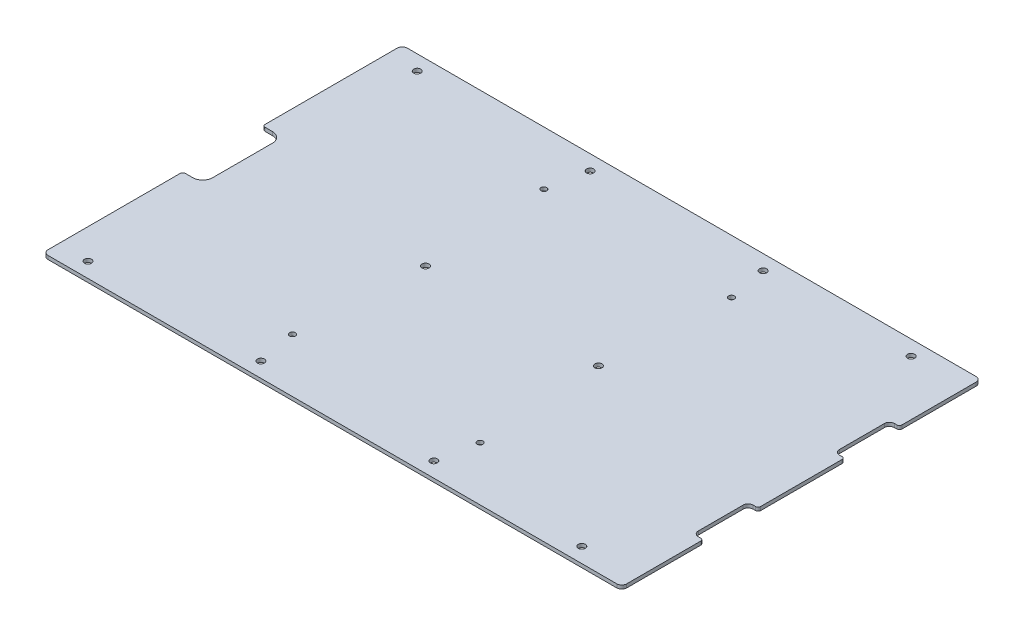
SolidWorks part; units mm, degrees
material "1060 Alloy"
ref_plane "Front" through (0, 0, 0) normal (0, 0, 1) x (1, 0, 0)
ref_plane "Top" through (0, 0, 0) normal (0, 1, 0) x (1, 0, 0)
ref_plane "Right" through (0, 0, 0) normal (1, 0, 0) x (0, 0, -1)
sketch "Sketch1" plane through (0, 0, 0) normal (0, 1, 0) x (1, 0, 0)
  line L0 (-55.0333, 0) -> (-165.1, 0) construction
  line L1 (-180.975, 114.3) -> (180.975, 114.3)
  line L2 (-184.15, 111.125) -> (-184.15, -111.125)
  line L3 (-180.975, -114.3) -> (180.975, -114.3)
  line L4 (184.15, 111.125) -> (184.15, -111.125)
  line L5 (-184.15, 114.3) -> (184.15, -114.3) construction
  line L6 (-184.15, -114.3) -> (184.15, 114.3) construction
  line L7 (-165.1, -104.775) -> (165.1, -104.775) construction
  line L8 (-165.1, -104.775) -> (-165.1, 104.775) construction
  line L9 (-165.1, 104.775) -> (165.1, 104.775) construction
  line L10 (165.1, -104.775) -> (165.1, 104.775) construction
  line L11 (-165.1, -104.775) -> (165.1, 104.775) construction
  line L12 (-165.1, 104.775) -> (165.1, -104.775) construction
  line L13 (-55.0333, -104.775) -> (55.0333, -104.775) construction
  line L14 (-55.0333, -104.775) -> (-55.0333, 104.775) construction
  line L15 (-55.0333, 104.775) -> (55.0333, 104.775) construction
  line L16 (55.0333, -104.775) -> (55.0333, 104.775) construction
  line L17 (-55.0333, -104.775) -> (55.0333, 104.775) construction
  line L18 (-55.0333, 104.775) -> (55.0333, -104.775) construction
  line L19 (55.0333, 0) -> (165.1, 0) construction
  line L20 (-55.0333, 0) -> (55.0333, 0) construction
  line L31 (-59.69, 80.01) -> (59.69, 80.01) construction
  line L32 (149.225, -104.775) -> (149.225, 104.775) construction
  line L33 (-59.69, 80.01) -> (-59.69, -80.01) construction
  line L34 (-59.69, -80.01) -> (59.69, -80.01) construction
  line L35 (59.69, 80.01) -> (59.69, -80.01) construction
  line L36 (-59.69, 80.01) -> (59.69, -80.01) construction
  line L37 (-59.69, -80.01) -> (59.69, 80.01) construction
  circle A0 centre (-165.1, 104.775) radius 2.2479
  circle A1 centre (-55.0333, 104.775) radius 2.2479
  circle A2 centre (55.0333, 104.775) radius 2.2479
  circle A3 centre (165.1, 104.775) radius 2.2479 construction
  circle A4 centre (165.1, -104.775) radius 2.2479 construction
  circle A5 centre (55.0333, -104.775) radius 2.2479
  circle A6 centre (-55.0333, -104.775) radius 2.2479
  circle A7 centre (-165.1, -104.775) radius 2.2479
  circle A12 centre (-55.0333, 0) radius 2.2479
  circle A13 centre (55.0333, 0) radius 2.2479
  arc A14 (184.15, 111.125) -> (180.975, 114.3) centre (180.975, 111.125) ccw
  arc A15 (184.15, -111.125) -> (180.975, -114.3) centre (180.975, -111.125) cw
  arc A16 (-180.975, -114.3) -> (-184.15, -111.125) centre (-180.975, -111.125) cw
  arc A17 (-180.975, 114.3) -> (-184.15, 111.125) centre (-180.975, 111.125) ccw
  circle A24 centre (149.225, -104.775) radius 2.2479
  circle A25 centre (149.225, 104.775) radius 2.2479
  circle A26 centre (59.69, -80.01) radius 1.8288
  circle A27 centre (-59.69, -80.01) radius 1.8288
  circle A28 centre (-59.69, 80.01) radius 1.8288
  circle A29 centre (59.69, 80.01) radius 1.8288
  point P0 (0, 0)
  point P6 (0, 0)
  point P11 (0, 0)
  point P28 (0, 0)
  point P29 (0, 0)
  point P32 (0, 0)
  dimension "D5" = 4.4958
  dimension "D8" = 3.6576
  dimension "D11" = 3.175
  dimension "D1" = 368.3
  dimension "D2" = 228.6
  dimension "D3" = 9.525
  dimension "D4" = 19.05
  dimension "D6" = 160.02
  dimension "D7" = 34.925
  dimension "D9" = 119.38
extrude "Boss-Extrude1" add sketch "Sketch1" along normal blind 2.286
sketch "Sketch2" plane through (0, 0, 0) normal (0, -1, 0) x (1, 0, 0)
  line L5 (184.15, 111.125) -> (184.15, -111.125) construction
  line L6 (184.15, 62.4205) -> (180.975, 62.4205)
  line L7 (184.15, 62.4205) -> (184.15, 27.4955)
  line L8 (184.15, 27.4955) -> (180.975, 27.4955)
  line L9 (177.8, 59.2455) -> (177.8, 30.6705)
  line L10 (-184.15, 0) -> (183.134, 0) construction
  line L11 (-184.15, -111.125) -> (-184.15, 111.125) construction
  line L12 (183.134, -115.824) -> (183.134, 115.824) construction
  line L13 (177.8, 44.958) -> (184.15, 44.958) construction
  line L14 (184.15, -27.4955) -> (180.975, -27.4955)
  line L15 (184.15, -62.4205) -> (184.15, -27.4955)
  line L16 (177.8, -59.2455) -> (177.8, -30.6705)
  line L17 (184.15, -62.4205) -> (180.975, -62.4205)
  line L19 (-184.15, 25.4) -> (-177.8, 25.4)
  line L20 (-184.15, 25.4) -> (-184.15, -25.4)
  line L21 (-184.15, -25.4) -> (-177.8, -25.4)
  line L22 (-171.45, 19.05) -> (-171.45, -19.05)
  arc A0 (180.975, -62.4205) -> (177.8, -59.2455) centre (180.975, -59.2455) cw
  arc A1 (177.8, -30.6705) -> (180.975, -27.4955) centre (180.975, -30.6705) cw
  arc A2 (177.8, 30.6705) -> (180.975, 27.4955) centre (180.975, 30.6705) ccw
  arc A3 (177.8, 59.2455) -> (180.975, 62.4205) centre (180.975, 59.2455) cw
  arc A4 (-171.45, -19.05) -> (-177.8, -25.4) centre (-177.8, -19.05) cw
  arc A5 (-171.45, 19.05) -> (-177.8, 25.4) centre (-177.8, 19.05) ccw
  point P20 (177.8, -62.4205)
  point P23 (177.8, -27.4955)
  point P26 (177.8, 27.4955)
  point P29 (177.8, 62.4205)
  point P38 (-171.45, 25.4)
  dimension "D4" = 3.175
  dimension "D7" = 6.35
  dimension "D1" = 34.925
  dimension "D2" = 44.958
  dimension "D3" = 6.35
  dimension "D5" = 50.8
  dimension "D6" = 12.7
extrude "Cut-Extrude1" cut sketch "Sketch2" against normal through all
fillet "Fillet1" radius 1.5875 6 edges at (184.15, 1.143, -62.4205) (184.15, 1.143, -27.4955) (184.15, 1.143, 27.4955) (184.15, 1.143, 62.4205) (-184.15, 1.143, -25.4) (-184.15, 1.143, 25.4)
